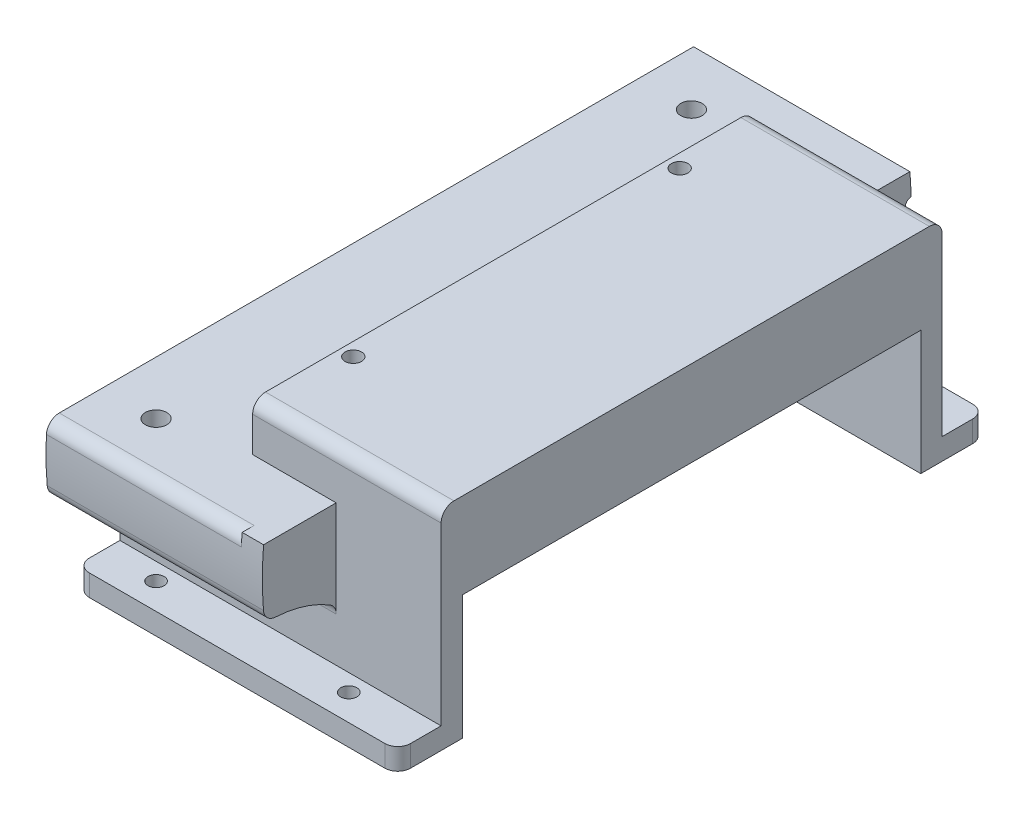
SolidWorks part; units mm, degrees
material "eSUN PLA+ (Not accurate)"
ref_plane "Front Plane" through (0, 0, 0) normal (0, 0, 1) x (1, 0, 0)
ref_plane "Top Plane" through (0, 0, 0) normal (0, 1, 0) x (1, 0, 0)
ref_plane "Right Plane" through (0, 0, 0) normal (1, 0, 0) x (0, 0, -1)
sketch "Sketch1" plane through (0, 0, 0) normal (1, 0, 0) x (0, 0, -1)
  line L2 (-68.627, 15.5) -> (-58.5, 15.5)
  line L6 (58.5, 15.5) -> (68.627, 15.5)
  line L19 (-53.1708, 39.4) -> (53, 39.4) construction
  line L26 (0, 15.1802) -> (0, 0) construction
  line L40 (-58.5, 15.5) -> (-58.5, 27.4809)
  line L45 (58.5, 15.5) -> (58.5, 27.4809)
  line L55 (-68.825, 44.85) -> (-68.825, 48.35) construction
  line L56 (-68.825, 35.35) -> (-68.825, 31.85)
  line L65 (53.5, 10.5) -> (69.1908, 10.5)
  line L66 (53.5, -5.6) -> (53.5, 10.5)
  line L67 (-53.5, -5.6) -> (-53.5, 10.5)
  line L68 (-53.5, -5.6) -> (53.5, -5.6)
  line L69 (-69.1908, 10.5) -> (-53.5, 10.5)
  line L70 (-68.627, 15.5) -> (-68.627, 10.5)
  line L71 (-68.627, 10.5) -> (68.627, 10.5)
  line L72 (68.627, 10.5) -> (68.627, 15.5)
  line L73 (-75.4487, 48.35) -> (-58.5, 48.35)
  line L74 (-58.5, 48.35) -> (-58.5, 59.5)
  line L75 (-58.5, 59.5) -> (58.5, 59.5)
  line L76 (58.5, 59.5) -> (58.5, 48.35)
  line L77 (58.5, 48.35) -> (75.4487, 48.35)
  arc A20 (63.8426, 0) -> (-63.8426, 0) centre (0, 41.6) ccw construction
  arc A21 (-75.4487, 48.35) -> (-75.1821, 32.3418) centre (0, 41.6) ccw
  arc A22 (-75.1821, 32.3418) -> (-58.5, 27.4809) centre (-74.0997, 5.0006) cw
  arc A23 (75.1821, 32.3418) -> (58.5, 27.4809) centre (74.0997, 5.0006) ccw
  arc A25 (75.4487, 48.35) -> (75.1821, 32.3418) centre (0, 41.6) cw
  circle A29 centre (0, 41.6) radius 76.2 construction
  arc A30 (-69.1908, 10.5) -> (69.1908, 10.5) centre (0, 41.025) ccw
  point P4 (0, -34.6)
  point P26 (-58.5, 27.4809)
  dimension "D14" = 3.5
  dimension "D5" = 49
  dimension "D2" = 29
  dimension "D4" = 152.4
  dimension "D6" = 152.4
  dimension "D1" = 151.5
  dimension "D13" = 5
  dimension "D15" = 3.5
  dimension "D3" = 16.1
  dimension "D11" = 45
  dimension "D16" = 117
extrude "Boss-Extrude1" add sketch "Sketch1" along normal blind 75 from offset 15 contours A25 A21 A22 L40 L2 L6 L45 A23 region at (0, 35.0798, 0)
sketch "Sketch2" plane through (90, 0, 0) normal (1, 0, 0) x (0, 0, -1)
  line L9 (68.627, 10.5) -> (-68.627, 10.5) construction
  line L26 (-53.5, 10.5) -> (53.5, 10.5)
  line L27 (-53.5, 10.5) -> (-53.5, 39.5)
  line L28 (-53.5, 39.5) -> (53.5, 39.5)
  line L29 (53.5, 10.5) -> (53.5, 39.5)
  point P5 (0, 10.5)
  dimension "D1" = 29
  dimension "D2" = 107
extrude "Cut-Extrude1" cut sketch "Sketch2" against normal through all
sketch "Sketch9" plane through (90, 0, 0) normal (1, 0, 0) x (0, 0, -1)
  line L9 (0, 0) -> (0, 23.2403) construction
  line L31 (-58.5, 27.4809) -> (-58.5, 48.35)
  line L32 (-58.5, 48.35) -> (-75.4487, 48.35)
  line L33 (58.5, 27.4809) -> (58.5, 48.35)
  line L34 (58.5, 48.35) -> (75.4487, 48.35)
  arc A9 (-75.4487, 48.35) -> (-75.1821, 32.3418) centre (0, 41.6) ccw
  arc A10 (-58.5, 27.4809) -> (-75.1821, 32.3418) centre (-74.0997, 5.0006) ccw construction
  arc A11 (-75.4487, 48.35) -> (-75.1821, 32.3418) centre (0, 41.6) ccw construction
  arc A12 (-75.1821, 32.3418) -> (-58.5, 27.4809) centre (-74.0997, 5.0006) cw
  arc A16 (75.1821, 32.3418) -> (58.5, 27.4809) centre (74.0997, 5.0006) ccw
  arc A17 (75.4487, 48.35) -> (75.1821, 32.3418) centre (0, 41.6) cw
  arc M125 (58.5, 27.4809) -> (75.1821, 32.3418) centre (74.0997, 5.0006) cw
  arc M126 (75.1821, 32.3418) -> (75.4487, 48.35) centre (0, 41.6) ccw
  dimension "D1" = 75.75
  dimension "D2" = 27.3626
extrude "Cut-Extrude12" cut sketch "Sketch9" against normal blind 29.5 from surface contours M125 M126 | A12 L31 L32 A9 region at (90, 39.6021, -66.6632) starting at face at (90, 30.8875, 0)
sketch "Sketch16" plane through (0, 10.5, 0) normal (0, -1, 0) x (1, 0, 0)
  line L0 (39.9, -62.5) -> (15, -62.5) construction
  line L2 (15, -53.5) -> (90, -53.5) construction
  line L3 (15, -68.627) -> (90, -68.627) construction
  line L4 (39.9, -62.5) -> (105, -62.5) construction
  line L7 (15, -58.5) -> (90, -58.5) construction
  line L8 (15, -68.627) -> (15, -53.5) construction
  line L10 (90, -68.627) -> (90, -53.5) construction
  circle A0 centre (27.45, -62.5) radius 1.875
  circle A1 centre (72.45, -62.5) radius 1.875
  point P16 (53.7494, -53.4453)
  point P20 (72.45, -62.5)
  point P22 (27.45, -62.5)
  dimension "D1" = 3.75
  dimension "D2" = 4
  dimension "D3" = 5
  dimension "D4" = 45
extrude "Cut-Extrude13" cut sketch "Sketch16" against normal up to surface (5 mm away) up to face at (52.5, 15.5, -63.5635)
mirror "Mirror2" about plane through (0, 0, 0) normal (0, 0, 1) of "Cut-Extrude13"
sketch "Sketch17" plane through (0, 59.5, 0) normal (0, 1, 0) x (1, 0, 0)
  line L7 (0, 58.5) -> (46, 58.5)
  line L8 (0, 58.5) -> (0, -58.5)
  line L9 (0, -58.5) -> (46, -58.5)
  line L10 (46, 58.5) -> (46, -58.5)
  point P2 (0, 0)
  dimension "D1" = 46
  dimension "D2" = 117
extrude "Cut-Extrude14" cut sketch "Sketch17" against normal up to surface (11.15 mm away) up to face at (37.75, 48.35, 66.9743)
sketch "Sketch14" plane through (0, 59.5, 0) normal (0, 1, 0) x (1, 0, 0)
  line L0 (90, 58.5) -> (90, -58.5) construction
  line L1 (49.1, 53.5) -> (49.1, -53.5) construction
  line L2 (90, -58.5) -> (46, -58.5) construction
  line L7 (-4.6951, 0) -> (11.3801, 0) construction
  circle A7 centre (49.1, 38.1) radius 1.93
  circle A8 centre (49.1, -38.1) radius 1.93
  dimension "D1" = 40.9
  dimension "D3" = 3.86
  dimension "D2" = 20.4
extrude "Cut-Extrude10" cut sketch "Sketch14" against normal blind 6.5 from surface contours A8 | A7 starting at face at (68, 59.5, 0)
sketch "Sketch18" [suppressed] plane through (0, 0, 0) normal (0, -1, 0) x (1, 0, 0)
  line L0 (0, -44) -> (0, -63.1262)
  line L1 (0, -44) -> (109.8, -44) construction
  line L3 (0, -44) -> (109.8, -44)
  circle A0 centre (82.35, -56.0631) radius 1.75 construction
  circle A1 centre (27.45, -56.0631) radius 1.75 construction
  circle A2 centre (82.35, -56.0631) radius 1.75
  circle A3 centre (27.45, -56.0631) radius 1.75
fillet "Fillet1" radius 3 11 edges at (37.75, 32.3418, -75.1821) (37.75, 32.3418, 75.1821) (90, 13, 68.627) (15, 13, 68.627) (15, 13, -68.627) (90, 13, -68.627) (37.75, 27.4809, 58.5) (37.75, 27.4809, -58.5) (68, 59.5, -58.5) (37.75, 48.35, 75.4487) (68, 59.5, 58.5)
ref_plane "Plane1" through (55.7, 0, 0) normal (1, 0, 0) x (0, 0, -1)
ref_plane "Plane2" through (35, 0, 0) normal (1, 0, 0) x (0, 0, -1)
sketch "Sketch20" plane through (60.5, 0, 0) normal (1, 0, 0) x (0, 0, -1)
  line L2 (75.4487, 48.35) -> (58.5, 48.35)
  line L6 (75.4487, 48.35) -> (58.5, 48.35)
  line L8 (58.5, 48.35) -> (58.5, 25.8521)
  line L10 (58.5, 48.35) -> (58.5, 25.8521)
  arc A5 (75.4672, 35.0609) -> (75.4487, 48.35) centre (0, 41.6) ccw
  arc A7 (75.4672, 35.0609) -> (75.4487, 48.35) centre (0, 41.6) ccw
  arc A18 (59.9485, 28.4197) -> (58.5, 25.8521) centre (61.5, 25.8521) ccw
  arc A20 (59.9485, 28.4197) -> (58.5, 25.8521) centre (61.5, 25.8521) ccw
  arc A21 (72.6386, 32.3242) -> (59.9485, 28.4197) centre (74.0997, 5.0006) ccw
  arc A22 (72.6386, 32.3242) -> (59.9485, 28.4197) centre (74.0997, 5.0006) ccw
  arc A23 (72.6386, 32.3242) -> (75.4672, 35.0609) centre (72.4784, 35.3199) ccw
  arc A24 (72.6386, 32.3242) -> (75.4672, 35.0609) centre (72.4784, 35.3199) ccw
  dimension "D1" = 0
extrude "Boss-Extrude3" add sketch "Sketch20" along normal blind 5
mirror "Mirror4" about plane through (0, 0, 0) normal (0, 0, 1) of "Boss-Extrude3"
sketch "Sketch21" plane through (65.5, 0, 0) normal (1, 0, 0) x (0, 0, -1)
  circle A0 centre (75.7499, 41.7059) radius 1.375
  arc A1 (75.4672, 35.0609) -> (75.4487, 48.35) centre (0, 41.6) ccw construction
  dimension "D1" = 2.75
extrude "Cut-Extrude15" cut sketch "Sketch21" against normal up to surface (50.5 mm away) up to face at (15, 27.1428, 3.491)
sketch "Sketch22" plane through (0, 15.5, 0) normal (0, 1, 0) x (1, 0, 0)
  circle A1 centre (27.45, -62.5) radius 1.875 construction
  circle A2 centre (27.45, -62.5) radius 2.5
  dimension "D1" = 5
extrude "Cut-Extrude16" cut sketch "Sketch22" along normal up to surface (32.85 mm away) up to face at (50.5, 48.35, 14.5307)
mirror "Mirror5" about plane through (0, 0, 0) normal (0, 0, 1) of "Cut-Extrude16"
sketch "Sketch23" plane through (46, 2.35, 0) normal (-1, 0, 0) x (0, 1, 0)
  line L0 (37.15, 59.5) -> (37.15, -59.5) construction
  line L2 (37.15, -59.5) -> (73.15, -59.5) construction
  line L3 (73.15, -59.5) -> (73.15, 59.5) construction
  line L4 (73.15, 59.5) -> (37.15, 59.5) construction
  line L5 (37.15, -49.5) -> (73.15, -49.5) construction
  line L6 (37.15, 49.5) -> (73.15, 49.5) construction
  line L7 (37.15, -49.5) -> (73.15, -59.5) construction
  line L8 (55.15, -49.5) -> (55.15, -59.5) construction
  line L9 (37.15, 59.5) -> (73.15, 49.5) construction
  line L10 (55.15, 59.5) -> (55.15, 49.5) construction
  circle A0 centre (55.15, 54.5) radius 1.93
  circle A1 centre (55.15, -54.5) radius 1.93
  dimension "D5" = 3.86
  dimension "D1" = 119
  dimension "D2" = 36
  dimension "D3" = 10
  dimension "D4" = 10
extrude "Cut-Extrude17" cut sketch "Sketch23" against normal blind 4
other "Intersect1" [suppressed]
ref_plane "Plane3" through (87, 0, 0) normal (1, 0, 0) x (0, 0, -1)
other "Intersect2" [suppressed]
